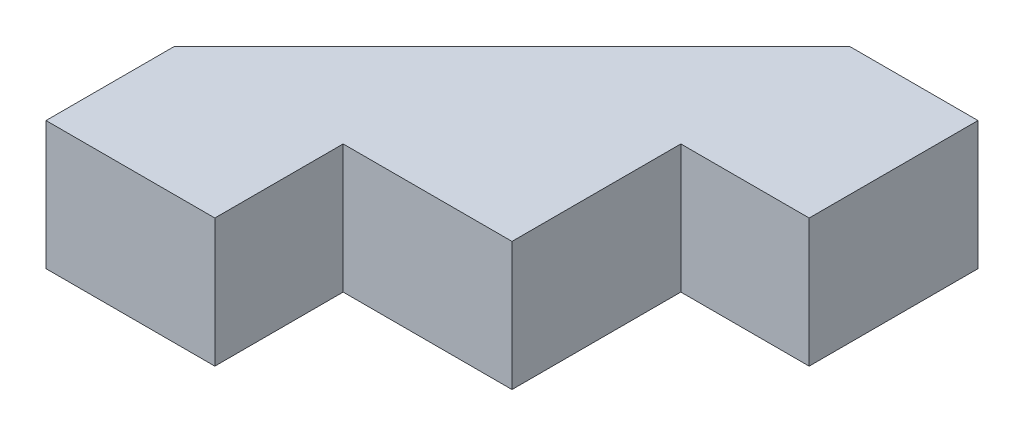
SolidWorks part; units mm, degrees
ref_plane "Front Plane" through (0, 0, 0) normal (0, 0, 1) x (1, 0, 0)
ref_plane "Top Plane" through (0, 0, 0) normal (0, 1, 0) x (1, 0, 0)
ref_plane "Right Plane" through (0, 0, 0) normal (1, 0, 0) x (0, 0, -1)
sketch "Sketch1" plane through (0, 0, 0) normal (0, 1, 0) x (1, 0, 0)
  line L0 (-8.362, -13.6221) -> (4.338, -0.9221)
  line L2 (4.338, -0.9221) -> (9.164, -0.9221)
  line L3 (-8.362, -13.6221) -> (4.338, -13.6221)
  line L4 (4.338, -0.9221) -> (4.338, -13.6221)
  line L5 (4.338, -0.9221) -> (4.338, -7.2721)
  line L6 (4.338, -7.2721) -> (9.164, -7.2721)
  line L7 (9.164, -0.9221) -> (9.164, -7.2721)
  line L8 (-8.362, -13.6221) -> (-2.012, -13.6221)
  line L9 (-8.362, -13.6221) -> (-8.362, -18.4481)
  line L10 (-8.362, -18.4481) -> (-2.012, -18.4481)
  line L11 (-2.012, -13.6221) -> (-2.012, -18.4481)
  dimension "D2" = 12.7
  dimension "D1" = 6.35
  dimension "D3" = 6.35
  dimension "D4" = 4.826
  dimension "D5" = 4.826
  dimension "D6" = 12.7
extrude "Boss-Extrude1" add sketch "Sketch1" along normal blind 4.826 contours L11 L3 L9 L10 | L4 L0 L3 | L7 L2 L4 L6 region at (0.1047, 0, 9.3888) region at (-5.187, 0, 16.0351) region at (6.751, 0, 4.0971)
equation "\"MDF\"= 0.19in"
equation "\"Foamcore\"= .13in"
equation "\"Gmaterial\"= \"MDF\""
equation "\"D4@Sketch1\"=\"MDF\""
equation "\"D5@Sketch1\"=\"MDF\""
equation "\"D1@Boss-Extrude1\"=\"MDF\""
equation "\"PVCID\" = 2.067in"
equation "\"PVCOD\" = 2.375in"
equation "\"GenDiameter\"= 60mm"
equation "\"GenCutDiameter\" = 1.8in"
equation "\"GenCutDistance\" = 1"
equation "\"TowerHeight\" = 6in"
equation "\"TowerFrontBase\" = 3in"
equation "\"FunnelHeight\" = 1in"
equation "\"FunnelAngle\" = 20"
equation "\"TowerSideBase\" = 3in"
equation "\"TowerPanelLength\" = 2in"
equation "\"TowerPanelLeeway\" = 0.5in"
equation "\"BaseLength\" = 9in"
equation "\"BaseWidth\" = 10in"
equation "\"WheelHoleLength\" = 3.25in"
equation "\"WheelHoleWidth\" = 26mm"
equation "\"WheelHoleFromBack\" = 1.5in"
equation "\"DropLength\" = 1in"
equation "\"DropWidth\" = 8.5in"
equation "\"BumperWidth\" = 1in"
equation "\"HoleDiameter\"= 0.25in"
equation "\"SmallHexDiameter\" = 0.185in"
equation "\"SmallHexHeight\" = 0.701in"
equation "\"ScrewSize\" = 0.106in"
equation "\"BigHexDiameter\" = 0.251in"
equation "\"BigHexHeight\" = 0.374in"
equation "\"PCBThickness\" = 0.066in"
equation "\"ConnectorHeight\" = 0.517in"
equation "\"BoardHeight\" = 0.583in"
equation "\"UnoStackHeight\" = 1.351in"
equation "\"UnoStackWidth\" = 3.053in"
equation "\"UnoStackLength\" = 3.152in"
equation "\"HBridgeWidth\" = 1.797in"
equation "\"HBridgeLength\" = 2.236in"
equation "\"DSWidth\" = 1.820in"
equation "\"DSLength\" = 1.833in"
equation "\"StepperWidth\" = 1.799in"
equation "\"StepperLength\" = 2.248in"
equation "\"ULNWidth\" = 1.304in"
equation "\"ULNLength\" = 1.545in"
equation "\"VSwitchHeight\" = 0.392in"
equation "\"VSwitchWidth\" = 0.637in"
equation "\"VSwitchLength\" = 1.097in"
equation "\"SkateWheelDiameter\" = 80mm"
equation "\"SkateWheelThickness\" = 24mm"
equation "\"BaseDistance\" = 3in"
